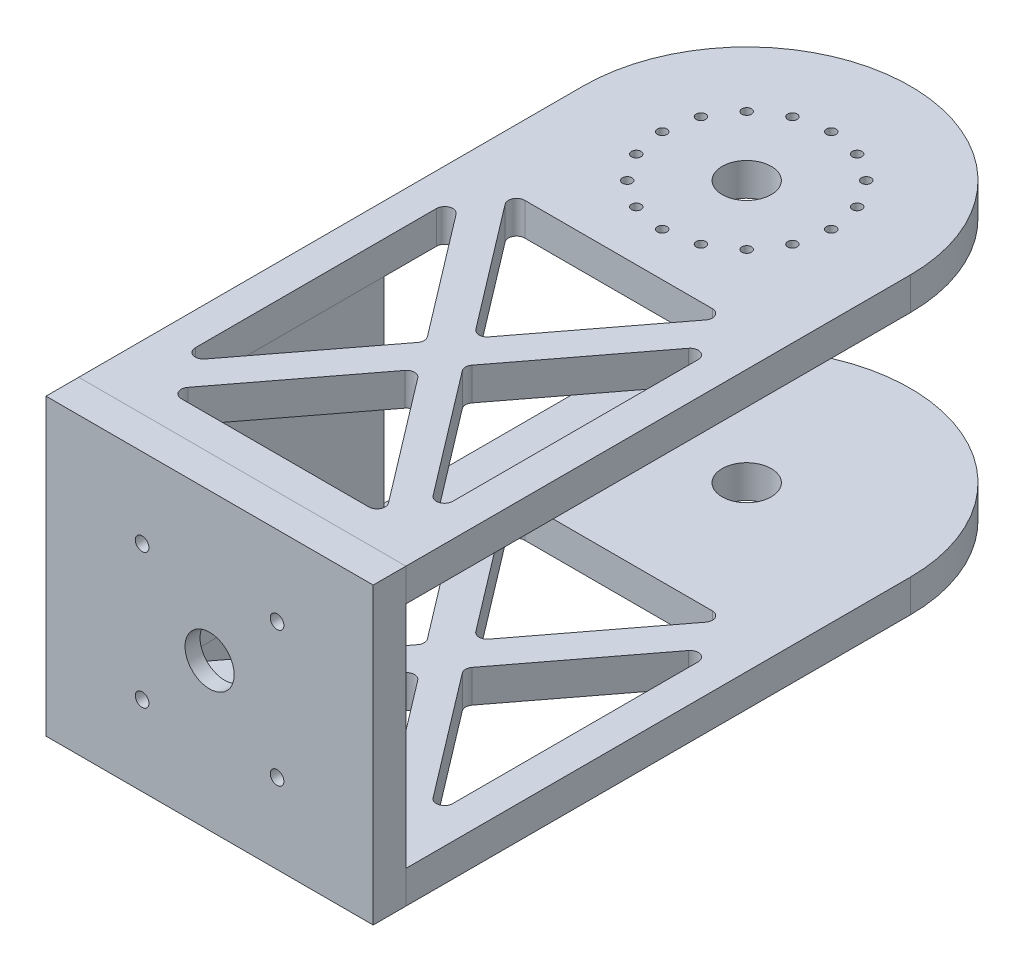
SolidWorks part; units mm, degrees
material "6061 Alloy"
ref_plane "Front Plane" through (0, 0, 0) normal (1, 0, 0) x (0, 1, 0)
ref_plane "Top Plane" through (0, 0, 0) normal (0, 0, 1) x (0, 1, 0)
ref_plane "Right Plane" through (0, 0, 0) normal (0, 1, 0) x (-1, 0, 0)
ref_axis "Axis1" through (0, -88.99, 0) along (0, 1, 0)
ref_axis "Axis2" through (55, 0, 0) along (-1, 0, 0)
sketch "Sketch1" plane through (0, 0, 0) normal (0, 1, 0) x (-1, 0, 0)
  line L1 (-60, 0) -> (60, 0)
  line L2 (-60, 0) -> (-60, 185)
  line L3 (-60, 185) -> (60, 185)
  line L4 (60, 0) -> (60, 185)
  line L5 (-60, 0) -> (60, 185) construction
  line L6 (-60, 185) -> (60, 0) construction
  circle A0 centre (0, 0) radius 9
  arc A1 (-60, 0) -> (60, 0) centre (0, 0) ccw
  arc A2 (-24.4627, 54.7866) -> (-60, 0) centre (0, 0) ccw construction
  arc A3 (24.4627, 54.7866) -> (-24.4627, 54.7866) centre (0, 0) ccw construction
  arc A4 (60, 0) -> (24.4627, 54.7866) centre (0, 0) ccw construction
  point P8 (0, 92.5)
  dimension "D1" = 18
  dimension "D2" = 120
  dimension "D3" = 185
extrude "Boss-Extrude1" add sketch "Sketch1" along normal blind 12 contours A0 L1 L4 L3 L2 | L1 A1 A0 region at (0, 0, 93.0112) region at (0, 0, -25.963)
sketch "Sketch2" plane through (0, 0, 0) normal (0, -1, 0) x (1, 0, 0)
  circle A0 centre (0, 0) radius 31 construction
  circle A1 centre (0, 31) radius 1.75
  circle A2 centre (11.8632, 28.6403) radius 1.75
  circle A3 centre (21.9203, 21.9203) radius 1.75
  circle A4 centre (28.6403, 11.8632) radius 1.75
  circle A5 centre (31, 0) radius 1.75
  circle A6 centre (28.6403, -11.8632) radius 1.75
  circle A7 centre (21.9203, -21.9203) radius 1.75
  circle A8 centre (11.8632, -28.6403) radius 1.75
  circle A9 centre (0, -31) radius 1.75
  circle A10 centre (-11.8632, -28.6403) radius 1.75
  circle A11 centre (-21.9203, -21.9203) radius 1.75
  circle A12 centre (-28.6403, -11.8632) radius 1.75
  circle A13 centre (-31, 0) radius 1.75
  circle A14 centre (-28.6403, 11.8632) radius 1.75
  circle A15 centre (-21.9203, 21.9203) radius 1.75
  circle A16 centre (-11.8632, 28.6403) radius 1.75
  point P37 (0, 0)
  dimension "D1" = 62
  dimension "D2" = 3.5
  dimension "D3" = 16
extrude "Cut-Extrude1" cut sketch "Sketch2" against normal blind 12
sketch "Sketch3" plane through (0, 0, 0) normal (0, -1, 0) x (1, 0, 0)
  line L0 (-60, 0) -> (-60, 185) construction
  line L1 (-60, 185) -> (-48, 185)
  line L2 (-60, 185) -> (-60, 85)
  line L3 (-60, 85) -> (-48, 85)
  line L4 (-48, 185) -> (-48, 85)
  line L5 (-60, 185) -> (-48, 85) construction
  line L6 (-60, 85) -> (-48, 185) construction
  line L8 (60, 185) -> (-60, 185) construction
  point P4 (-54, 135)
  dimension "D1" = 12
  dimension "D3" = 100
extrude "ss" add sketch "Sketch3" along normal blind 84 separate body
extrude "Boss-Extrude3" add sketch "Sketch1<3>" against normal blind 12 from surface separate body contours A0 L1 L4 L3 L2 | L1 A1 A0 region at (0, 0, 93.0112) region at (0, 0, -25.963) starting at face at (-54, -84, 135)
sketch "Sketch1<3>" plane through (0, 0, 0) normal (0, 1, 0) x (-1, 0, 0) same geometry as "Sketch1"
sketch "Sketch4" plane through (0, 0, 185) normal (0, 0, 1) x (1, 0, 0)
  line L1 (-60, 12) -> (60, 12)
  line L2 (-60, 12) -> (-60, -96)
  line L3 (-60, -96) -> (60, -96)
  line L4 (60, 12) -> (60, -96)
  line L5 (-60, 12) -> (60, -96) construction
  line L6 (-60, -96) -> (60, 12) construction
  point P4 (0, -42)
extrude "Boss-Extrude4" add sketch "Sketch4" along normal blind 12 separate body
sketch "Sketch5" plane through (0, 0, 185) normal (0, 0, -1) x (1, 0, 0)
  line L0 (-60, -12) -> (60, 96) construction
  line L1 (60, 96) -> (-60, 96) construction
  line L2 (-60, 96) -> (60, -12) construction
  line L3 (-60, -12) -> (60, -12) construction
  line L5 (-35, 77) -> (35, 77)
  line L6 (-35, 77) -> (-35, 7)
  line L7 (-35, 7) -> (35, 7)
  line L8 (35, 77) -> (35, 7)
  line L9 (-35, 77) -> (35, 7) construction
  line L10 (-35, 7) -> (35, 77) construction
  circle A0 centre (0, 42) radius 9
  circle A1 centre (0, 42) radius 35 construction
  circle A2 centre (-24.7487, 66.7487) radius 2.5
  circle A3 centre (24.7487, 66.7487) radius 2.5
  circle A4 centre (24.7487, 17.2513) radius 2.5
  circle A5 centre (-24.7487, 17.2513) radius 2.5
  circle A6 centre (0, 42) radius 25
  dimension "D1" = 18
  dimension "D2" = 70
  dimension "D4" = 5
  dimension "D6" = 50
  dimension "D3" = 70
  dimension "D5" = 4
extrude "Cut-Extrude2" cut sketch "Sketch5" against normal through all both and the other way through all contours A0 | A3 | A2 | A5 | A4
extrude "Cut-Extrude3" cut sketch "Sketch5<3>" against normal blind 3 contours L5 L8 L7 L6
sketch "Sketch5<3>" plane through (0, 0, 185) normal (0, 0, -1) x (1, 0, 0) same geometry as "Sketch5"
extrude "Cut-Extrude4" cut sketch "Sketch5<4>" against normal blind 3.5 from surface contours A6 starting at face at (0, -42, 188)
sketch "Sketch5<4>" plane through (0, 0, 185) normal (0, 0, -1) x (1, 0, 0) same geometry as "Sketch5"
fillet "Fillet1" radius 6 4 edges at (35, -77, 186.5) (35, -7, 186.5) (-35, -7, 186.5) (-35, -77, 186.5)
sketch "Sketch6" plane through (0, 12, 0) normal (0, 1, 0) x (1, 0, 0)
  line L0 (60, -47) -> (48, -47) construction
  line L1 (60, 0) -> (60, -185) construction
  line L2 (-60, 0) -> (-60, -185) construction
  line L3 (60, -173) -> (48, -173) construction
  line L4 (60, -185) -> (-60, -185) construction
  line L5 (48, -160.4) -> (-4.1906, -105.5999) construction
  line L6 (36.786, -168.1819) -> (2.3863, -123.0323)
  line L7 (34.3997, -47) -> (-34.3997, -47)
  line L8 (48, -65.7879) -> (48, -155.8291)
  line L9 (34.3997, -173) -> (-34.3997, -173)
  line L10 (-48, -65.7879) -> (-48, -154.2121)
  line L11 (48, -47) -> (3.1555, -105.8584) construction
  line L12 (0, -110) -> (-3.7715, -105.0499) construction
  line L13 (0, -59.4) -> (0, 59.4) construction
  line L14 (42.6137, -157.6472) -> (8.3123, -112.6266)
  line L15 (-2.3863, -123.0323) -> (-36.786, -168.1819)
  line L16 (8.3123, -108.9904) -> (42.6137, -63.9698)
  line L17 (36.786, -51.8181) -> (2.3863, -96.9677)
  line L18 (-2.3863, -96.9677) -> (-36.786, -51.8181)
  line L19 (-8.9283, -108.1819) -> (-42.6137, -63.9698)
  line L20 (-3.7715, -105.0499) -> (-4.1906, -105.5999)
  line L21 (0, -119.9003) -> (-3.7715, -114.9501) construction
  line L22 (0, -110) -> (-3.7715, -114.9501) construction
  line L23 (-3.7715, -114.9501) -> (-48, -173) construction
  line L24 (-3.7715, -114.9501) -> (-7.5431, -110) construction
  line L25 (-4.1906, -105.5999) -> (-7.5431, -110) construction
  line L26 (-8.9283, -111.8181) -> (-42.6137, -156.0302)
  line L27 (-4.1906, -105.5999) -> (-37.7154, -70.3989) construction
  line L28 (-37.7154, -70.3989) -> (-60, -47) construction
  line L29 (-3.7715, -105.0499) -> (-48, -47) construction
  line L30 (0, -100.0997) -> (-3.7715, -105.0499) construction
  line L31 (3.1555, -105.8584) -> (0, -110) construction
  line L32 (6.9271, -110.8085) -> (3.1555, -105.8584) construction
  line L33 (48, -47) -> (40.4569, -47) construction
  line L34 (48, -47) -> (40.4569, -47) construction
  line L35 (40.4569, -47) -> (-40.4569, -47) construction
  line L36 (48, -47) -> (48, -56.9003) construction
  line L37 (-40.4569, -47) -> (-48, -47) construction
  line L38 (-48, -47) -> (-60, -47) construction
  line L39 (-40.4569, -47) -> (-48, -47) construction
  line L40 (-48, -47) -> (-48, -56.9003) construction
  line L41 (-48, -163.0997) -> (-48, -173) construction
  line L42 (-40.4569, -173) -> (-48, -173) construction
  line L43 (-40.4569, -173) -> (-48, -173) construction
  line L44 (-48, -173) -> (-60, -173) construction
  line L45 (48, -173) -> (40.4569, -173) construction
  line L46 (48, -173) -> (40.4569, -173) construction
  line L47 (40.4569, -173) -> (-40.4569, -173) construction
  line L48 (48, -173) -> (0, -110) construction
  line L49 (48, -164.7168) -> (48, -173) construction
  line L50 (60, -173) -> (48, -160.4) construction
  circle A0 centre (0, -31) radius 1.75 construction
  arc A1 (-36.786, -168.1819) -> (-34.3997, -173) centre (-34.3997, -170) ccw
  arc A2 (-42.6137, -156.0302) -> (-48, -154.2121) centre (-45, -154.2121) cw
  arc A3 (-36.786, -51.8181) -> (-34.3997, -47) centre (-34.3997, -50) cw
  arc A4 (-42.6137, -63.9698) -> (-48, -65.7879) centre (-45, -65.7879) ccw
  arc A5 (2.3863, -123.0323) -> (-2.3863, -123.0323) centre (0, -124.8504) ccw
  arc A6 (-8.9283, -108.1819) -> (-8.9283, -111.8181) centre (-11.3146, -110) cw
  arc A7 (2.3863, -96.9677) -> (-2.3863, -96.9677) centre (0, -95.1496) cw
  arc A8 (8.3123, -108.9904) -> (8.3123, -112.6266) centre (10.6986, -110.8085) ccw
  arc A9 (36.786, -51.8181) -> (34.3997, -47) centre (34.3997, -50) ccw
  arc A10 (42.6137, -63.9698) -> (48, -65.7879) centre (45, -65.7879) cw
  arc A11 (36.786, -168.1819) -> (34.3997, -173) centre (34.3997, -170) cw
  arc A12 (42.6137, -157.6472) -> (48, -155.8291) centre (45, -155.8291) ccw
  point P12 (0, -110)
  dimension "D6" = 3
  dimension "D1" = 16
  dimension "D2" = 12
  dimension "D3" = 12
  dimension "D4" = 6
  dimension "D5" = 6
extrude "Cut-Extrude5" cut sketch "Sketch6" against normal through all both and the other way through all contours L16 A10 L8 A12 L14 A8 | L17 A7 L18 A3 L7 A9 | L10 A2 L26 A6 L19 A4 | L9 A1 L15 A5 L6 A11
